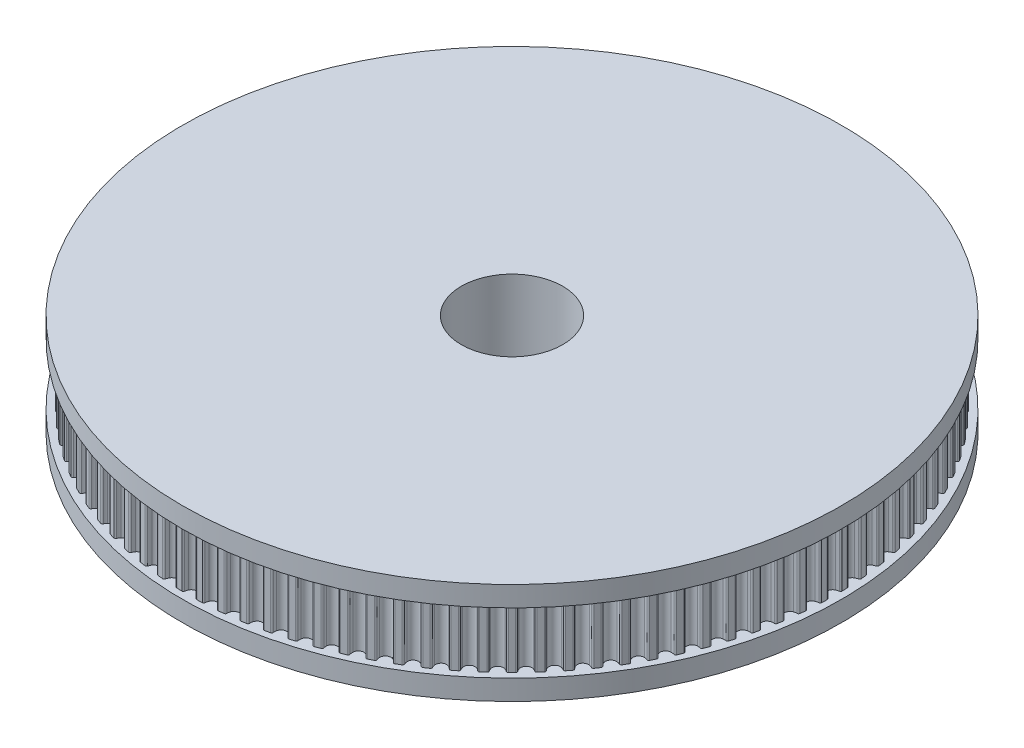
SolidWorks part; units mm, degrees
ref_plane "Front Plane" through (0, 0, 0) normal (0, 0, 1) x (1, 0, 0)
ref_plane "Top Plane" through (0, 0, 0) normal (0, 1, 0) x (1, 0, 0)
ref_plane "Right Plane" through (0, 0, 0) normal (1, 0, 0) x (0, 0, -1)
sketch "Sketch1" plane through (0, 0, 0) normal (0, 1, 0) x (1, 0, 0)
  arc A0 (-0.7485, 6.3218) -> (0.7485, 6.3218) centre (0, 0) ccw
  arc A3 (0.5071, 5.943) -> (0.5827, 6.1964) centre (-0.4049, 6.3531) ccw
  arc A4 (-0.5071, 5.943) -> (0.5071, 5.943) centre (0, 6.171) ccw
  arc A5 (-0.5827, 6.1964) -> (-0.5071, 5.943) centre (0.4049, 6.3531) ccw
  arc A6 (0.7485, 6.3218) -> (0.5827, 6.1964) centre (0.7309, 6.1729) ccw
  arc A7 (-0.7485, 6.3218) -> (-0.5827, 6.1964) centre (-0.7309, 6.1729) cw
  arc A8 (1.2417, 6.2437) -> (1.3606, 6.0732) centre (1.2124, 6.0966) cw
  arc A9 (1.3606, 6.0732) -> (1.3542, 5.8088) centre (2.3483, 5.917) ccw
  arc A10 (1.3542, 5.8088) -> (2.3187, 5.4954) centre (1.9069, 5.869) ccw
  arc A11 (2.3187, 5.4954) -> (2.469, 5.7131) centre (1.5781, 6.1673) ccw
  arc A12 (2.6654, 5.7811) -> (2.469, 5.7131) centre (2.6026, 5.6449) ccw
  arc A13 (3.1103, 5.5544) -> (3.1707, 5.3555) centre (3.0371, 5.4236) cw
  arc A14 (3.1707, 5.3555) -> (3.0829, 5.106) centre (4.0619, 4.9018) ccw
  arc A15 (3.0829, 5.106) -> (3.9034, 4.5099) centre (3.6272, 4.9924) ccw
  arc A16 (3.9034, 4.5099) -> (4.1136, 4.6705) centre (3.4067, 5.3778) ccw
  arc A17 (4.3214, 4.6745) -> (4.1136, 4.6705) centre (4.2196, 4.5644) ccw
  arc A18 (4.6745, 4.3214) -> (4.6705, 4.1136) centre (4.5644, 4.2196) cw
  arc A19 (4.6705, 4.1136) -> (4.5099, 3.9034) centre (5.3778, 3.4067) ccw
  arc A20 (4.5099, 3.9034) -> (5.106, 3.0829) centre (4.9924, 3.6272) ccw
  arc A21 (5.106, 3.0829) -> (5.3555, 3.1707) centre (4.9018, 4.0619) ccw
  arc A22 (5.5544, 3.1103) -> (5.3555, 3.1707) centre (5.4236, 3.0371) ccw
  arc A23 (5.7811, 2.6654) -> (5.7131, 2.469) centre (5.6449, 2.6026) cw
  arc A24 (5.7131, 2.469) -> (5.4954, 2.3187) centre (6.1673, 1.5781) ccw
  arc A25 (5.4954, 2.3187) -> (5.8088, 1.3542) centre (5.869, 1.9069) ccw
  arc A26 (5.8088, 1.3542) -> (6.0732, 1.3606) centre (5.917, 2.3483) ccw
  arc A27 (6.2437, 1.2417) -> (6.0732, 1.3606) centre (6.0966, 1.2124) ccw
  arc A28 (6.3218, 0.7485) -> (6.1964, 0.5827) centre (6.1729, 0.7309) cw
  arc A29 (6.1964, 0.5827) -> (5.943, 0.5071) centre (6.3531, -0.4049) ccw
  arc A30 (5.943, 0.5071) -> (5.943, -0.5071) centre (6.171, 0) ccw
  arc A31 (5.943, -0.5071) -> (6.1964, -0.5827) centre (6.3531, 0.4049) ccw
  arc A32 (6.3218, -0.7485) -> (6.1964, -0.5827) centre (6.1729, -0.7309) ccw
  arc A33 (6.2437, -1.2417) -> (6.0732, -1.3606) centre (6.0966, -1.2124) cw
  arc A34 (6.0732, -1.3606) -> (5.8088, -1.3542) centre (5.917, -2.3483) ccw
  arc A35 (5.8088, -1.3542) -> (5.4954, -2.3187) centre (5.869, -1.9069) ccw
  arc A36 (5.4954, -2.3187) -> (5.7131, -2.469) centre (6.1673, -1.5781) ccw
  arc A37 (5.7811, -2.6654) -> (5.7131, -2.469) centre (5.6449, -2.6026) ccw
  arc A38 (5.5544, -3.1103) -> (5.3555, -3.1707) centre (5.4236, -3.0371) cw
  arc A39 (5.3555, -3.1707) -> (5.106, -3.0829) centre (4.9018, -4.0619) ccw
  arc A40 (5.106, -3.0829) -> (4.5099, -3.9034) centre (4.9924, -3.6272) ccw
  arc A41 (4.5099, -3.9034) -> (4.6705, -4.1136) centre (5.3778, -3.4067) ccw
  arc A42 (4.6745, -4.3214) -> (4.6705, -4.1136) centre (4.5644, -4.2196) ccw
  arc A43 (4.3214, -4.6745) -> (4.1136, -4.6705) centre (4.2196, -4.5644) cw
  arc A44 (4.1136, -4.6705) -> (3.9034, -4.5099) centre (3.4067, -5.3778) ccw
  arc A45 (3.9034, -4.5099) -> (3.0829, -5.106) centre (3.6272, -4.9924) ccw
  arc A46 (3.0829, -5.106) -> (3.1707, -5.3555) centre (4.0619, -4.9018) ccw
  arc A47 (3.1103, -5.5544) -> (3.1707, -5.3555) centre (3.0371, -5.4236) ccw
  arc A48 (2.6654, -5.7811) -> (2.469, -5.7131) centre (2.6026, -5.6449) cw
  arc A49 (2.469, -5.7131) -> (2.3187, -5.4954) centre (1.5781, -6.1673) ccw
  arc A50 (2.3187, -5.4954) -> (1.3542, -5.8088) centre (1.9069, -5.869) ccw
  arc A51 (1.3542, -5.8088) -> (1.3606, -6.0732) centre (2.3483, -5.917) ccw
  arc A52 (1.2417, -6.2437) -> (1.3606, -6.0732) centre (1.2124, -6.0966) ccw
  arc A53 (0.7485, -6.3218) -> (0.5827, -6.1964) centre (0.7309, -6.1729) cw
  arc A54 (0.5827, -6.1964) -> (0.5071, -5.943) centre (-0.4049, -6.3531) ccw
  arc A55 (0.5071, -5.943) -> (-0.5071, -5.943) centre (0, -6.171) ccw
  arc A56 (-0.5071, -5.943) -> (-0.5827, -6.1964) centre (0.4049, -6.3531) ccw
  arc A57 (-0.7485, -6.3218) -> (-0.5827, -6.1964) centre (-0.7309, -6.1729) ccw
  arc A58 (-1.2417, -6.2437) -> (-1.3606, -6.0732) centre (-1.2124, -6.0966) cw
  arc A59 (-1.3606, -6.0732) -> (-1.3542, -5.8088) centre (-2.3483, -5.917) ccw
  arc A60 (-1.3542, -5.8088) -> (-2.3187, -5.4954) centre (-1.9069, -5.869) ccw
  arc A61 (-2.3187, -5.4954) -> (-2.469, -5.7131) centre (-1.5781, -6.1673) ccw
  arc A62 (-2.6654, -5.7811) -> (-2.469, -5.7131) centre (-2.6026, -5.6449) ccw
  arc A63 (-3.1103, -5.5544) -> (-3.1707, -5.3555) centre (-3.0371, -5.4236) cw
  arc A64 (-3.1707, -5.3555) -> (-3.0829, -5.106) centre (-4.0619, -4.9018) ccw
  arc A65 (-3.0829, -5.106) -> (-3.9034, -4.5099) centre (-3.6272, -4.9924) ccw
  arc A66 (-3.9034, -4.5099) -> (-4.1136, -4.6705) centre (-3.4067, -5.3778) ccw
  arc A67 (-4.3214, -4.6745) -> (-4.1136, -4.6705) centre (-4.2196, -4.5644) ccw
  arc A68 (-4.6745, -4.3214) -> (-4.6705, -4.1136) centre (-4.5644, -4.2196) cw
  arc A69 (-4.6705, -4.1136) -> (-4.5099, -3.9034) centre (-5.3778, -3.4067) ccw
  arc A70 (-4.5099, -3.9034) -> (-5.106, -3.0829) centre (-4.9924, -3.6272) ccw
  arc A71 (-5.106, -3.0829) -> (-5.3555, -3.1707) centre (-4.9018, -4.0619) ccw
  arc A72 (-5.5544, -3.1103) -> (-5.3555, -3.1707) centre (-5.4236, -3.0371) ccw
  arc A73 (-5.7811, -2.6654) -> (-5.7131, -2.469) centre (-5.6449, -2.6026) cw
  arc A74 (-5.7131, -2.469) -> (-5.4954, -2.3187) centre (-6.1673, -1.5781) ccw
  arc A75 (-5.4954, -2.3187) -> (-5.8088, -1.3542) centre (-5.869, -1.9069) ccw
  arc A76 (-5.8088, -1.3542) -> (-6.0732, -1.3606) centre (-5.917, -2.3483) ccw
  arc A77 (-6.2437, -1.2417) -> (-6.0732, -1.3606) centre (-6.0966, -1.2124) ccw
  arc A78 (-6.3218, -0.7485) -> (-6.1964, -0.5827) centre (-6.1729, -0.7309) cw
  arc A79 (-6.1964, -0.5827) -> (-5.943, -0.5071) centre (-6.3531, 0.4049) ccw
  arc A80 (-5.943, -0.5071) -> (-5.943, 0.5071) centre (-6.171, 0) ccw
  arc A81 (-5.943, 0.5071) -> (-6.1964, 0.5827) centre (-6.3531, -0.4049) ccw
  arc A82 (-6.3218, 0.7485) -> (-6.1964, 0.5827) centre (-6.1729, 0.7309) ccw
  arc A83 (-6.2437, 1.2417) -> (-6.0732, 1.3606) centre (-6.0966, 1.2124) cw
  arc A84 (-6.0732, 1.3606) -> (-5.8088, 1.3542) centre (-5.917, 2.3483) ccw
  arc A85 (-5.8088, 1.3542) -> (-5.4954, 2.3187) centre (-5.869, 1.9069) ccw
  arc A86 (-5.4954, 2.3187) -> (-5.7131, 2.469) centre (-6.1673, 1.5781) ccw
  arc A87 (-5.7811, 2.6654) -> (-5.7131, 2.469) centre (-5.6449, 2.6026) ccw
  arc A88 (-5.5544, 3.1103) -> (-5.3555, 3.1707) centre (-5.4236, 3.0371) cw
  arc A89 (-5.3555, 3.1707) -> (-5.106, 3.0829) centre (-4.9018, 4.0619) ccw
  arc A90 (-5.106, 3.0829) -> (-4.5099, 3.9034) centre (-4.9924, 3.6272) ccw
  arc A91 (-4.5099, 3.9034) -> (-4.6705, 4.1136) centre (-5.3778, 3.4067) ccw
  arc A92 (-4.6745, 4.3214) -> (-4.6705, 4.1136) centre (-4.5644, 4.2196) ccw
  arc A93 (-4.3214, 4.6745) -> (-4.1136, 4.6705) centre (-4.2196, 4.5644) cw
  arc A94 (-4.1136, 4.6705) -> (-3.9034, 4.5099) centre (-3.4067, 5.3778) ccw
  arc A95 (-3.9034, 4.5099) -> (-3.0829, 5.106) centre (-3.6272, 4.9924) ccw
  arc A96 (-3.0829, 5.106) -> (-3.1707, 5.3555) centre (-4.0619, 4.9018) ccw
  arc A97 (-3.1103, 5.5544) -> (-3.1707, 5.3555) centre (-3.0371, 5.4236) ccw
  arc A98 (-2.6654, 5.7811) -> (-2.469, 5.7131) centre (-2.6026, 5.6449) cw
  arc A99 (-2.469, 5.7131) -> (-2.3187, 5.4954) centre (-1.5781, 6.1673) ccw
  arc A100 (-2.3187, 5.4954) -> (-1.3542, 5.8088) centre (-1.9069, 5.869) ccw
  arc A101 (-1.3542, 5.8088) -> (-1.3606, 6.0732) centre (-2.3483, 5.917) ccw
  arc A102 (-1.2417, 6.2437) -> (-1.3606, 6.0732) centre (-1.2124, 6.0966) ccw
  circle A103 centre (0, 0) radius 5
  point P5 (0, 6.366)
  point P225 (0, 0)
  dimension "D1" = 12.732
  dimension "D2" = 0.15
  dimension "D4" = 20
  dimension "D5" = 2
  dimension "D6" = 10
  dimension "D3" = 0.195
extrude "Boss-Extrude1" add sketch "Sketch1" along normal blind 12 contours A0 A102 A101 A100 A99 A98 A97 A96 A95 A94 A93 A92 A91 A90 A89 A88 A87 A86 A85 A84 A83 A82 A81 A80 A79 A78 A77 A76 A75 A74 A73 A72 A71 A70 A69 A68 A67 A66 A65 A64 A63 A62 A61 region at (-0.7483, 0, -6.1499)
sketch "Sketch2" plane through (0, 12, 0) normal (0, 1, 0) x (1, 0, 0)
  arc A0 (-0.7427, 31.8213) -> (0.7427, 31.8213) centre (0, 0) ccw
  arc A1 (-0.501, 31.394) -> (0.501, 31.394) centre (0, 31.635) ccw
  arc A2 (0.501, 31.394) -> (0.5906, 31.6917) centre (-0.4001, 31.8275) ccw
  arc A4 (-0.5906, 31.6917) -> (-0.501, 31.394) centre (0.4001, 31.8275) ccw
  arc A5 (0.7427, 31.8213) -> (0.5906, 31.6917) centre (0.7392, 31.6714) ccw
  arc A6 (-0.7427, 31.8213) -> (-0.5906, 31.6917) centre (-0.7392, 31.6714) cw
  arc A7 (1.4005, 31.6663) -> (1.4712, 31.3635) centre (2.3978, 31.7396) ccw
  arc A8 (1.2568, 31.8052) -> (1.4005, 31.6663) centre (1.2509, 31.6553) cw
  arc A9 (1.4712, 31.3635) -> (2.4713, 31.3006) centre (1.9864, 31.5726) ccw
  arc A10 (2.4713, 31.3006) -> (2.5794, 31.5921) centre (1.5991, 31.7898) ccw
  arc A11 (2.7394, 31.7119) -> (2.5794, 31.5921) centre (2.7265, 31.5625) ccw
  arc A12 (3.386, 31.5159) -> (3.4376, 31.2092) centre (4.386, 31.5264) ccw
  arc A13 (3.2514, 31.6635) -> (3.386, 31.5159) centre (3.2361, 31.5143) cw
  arc A14 (3.4376, 31.2092) -> (4.4318, 31.0836) centre (3.9649, 31.3855) ccw
  arc A15 (4.4318, 31.0836) -> (4.558, 31.3678) centre (3.5921, 31.6267) ccw
  arc A16 (4.7252, 31.4773) -> (4.558, 31.3678) centre (4.7029, 31.329) ccw
  arc A17 (5.3583, 31.2411) -> (5.3905, 30.9318) centre (6.3569, 31.1888) ccw
  arc A18 (5.2331, 31.3969) -> (5.3583, 31.2411) centre (5.2085, 31.2489) cw
  arc A19 (5.3905, 30.9318) -> (6.3748, 30.744) centre (5.9278, 31.0747) ccw
  arc A20 (6.3748, 30.744) -> (6.5186, 31.0197) centre (5.5709, 31.3387) ccw
  arc A21 (6.6923, 31.1185) -> (6.5186, 31.0197) centre (6.6608, 30.9719) ccw
  arc A22 (7.3093, 30.843) -> (7.3221, 30.5323) centre (8.3027, 30.7281) ccw
  arc A23 (7.1942, 31.0063) -> (7.3093, 30.843) centre (7.1603, 30.8602) cw
  arc A24 (7.3221, 30.5323) -> (8.2927, 30.2831) centre (7.8673, 30.6411) ccw
  arc A25 (8.2927, 30.2831) -> (8.4535, 30.5492) centre (7.5276, 30.9271) ccw
  arc A26 (8.6331, 30.6369) -> (8.4535, 30.5492) centre (8.5924, 30.4925) ccw
  arc A27 (9.2316, 30.3231) -> (9.2248, 30.0123) centre (10.2158, 30.1461) ccw
  arc A28 (9.1269, 30.4934) -> (9.2316, 30.3231) centre (9.0839, 30.3497) cw
  arc A29 (9.2248, 30.0123) -> (10.1778, 29.7026) centre (9.7758, 30.0867) ccw
  arc A30 (10.1778, 29.7026) -> (10.355, 29.9581) centre (9.4547, 30.3934) ccw
  arc A31 (10.5397, 30.0344) -> (10.355, 29.9581) centre (10.4901, 29.8928) ccw
  arc A32 (11.1173, 29.6837) -> (11.091, 29.3738) centre (12.0885, 29.4452) ccw
  arc A33 (11.0236, 29.8602) -> (11.1173, 29.6837) centre (10.9717, 29.7194) cw
  arc A34 (11.091, 29.3738) -> (12.0227, 29.0049) centre (11.6456, 29.4135) ccw
  arc A35 (12.0227, 29.0049) -> (12.2157, 29.2488) centre (11.3445, 29.7397) ccw
  arc A36 (12.4048, 29.3133) -> (12.2157, 29.2488) centre (12.3463, 29.1752) ccw
  arc A37 (12.9593, 28.927) -> (12.9135, 28.6194) centre (13.9135, 28.628) ccw
  arc A38 (12.8768, 29.109) -> (12.9593, 28.927) centre (12.8161, 28.9719) cw
  arc A39 (12.9135, 28.6194) -> (13.8202, 28.1928) centre (13.4695, 28.6242) ccw
  arc A40 (13.8202, 28.1928) -> (14.0281, 28.4241) centre (13.1895, 28.9687) ccw
  arc A41 (14.2209, 28.4766) -> (14.0281, 28.4241) centre (14.1539, 28.3424) ccw
  arc A42 (14.75, 28.0562) -> (14.6851, 27.7521) centre (15.6836, 27.6979) ccw
  arc A43 (14.6792, 28.2431) -> (14.75, 28.0562) centre (14.61, 28.11) cw
  arc A44 (14.6851, 27.7521) -> (15.5632, 27.2694) centre (15.2403, 27.722) ccw
  arc A45 (15.5632, 27.2694) -> (15.7852, 27.4871) centre (14.9824, 28.0834) ccw
  arc A46 (15.9809, 27.5274) -> (15.7852, 27.4871) centre (15.9056, 27.3977) ccw
  arc A47 (16.4826, 27.0747) -> (16.3987, 26.7753) centre (17.3918, 26.6584) ccw
  arc A48 (16.4236, 27.2656) -> (16.4826, 27.0747) centre (16.3462, 27.1371) cw
  arc A49 (16.3987, 26.7753) -> (17.2448, 26.2383) centre (16.9509, 26.7103) ccw
  arc A50 (17.2448, 26.2383) -> (17.48, 26.4417) centre (16.7162, 27.0872) ccw
  arc A51 (17.6778, 26.4697) -> (17.48, 26.4417) centre (17.5945, 26.3449) ccw
  arc A52 (18.1501, 25.9863) -> (18.0476, 25.6927) centre (19.0314, 25.5138) ccw
  arc A53 (18.1032, 26.1806) -> (18.1501, 25.9863) centre (18.0179, 26.0572) cw
  arc A54 (18.0476, 25.6927) -> (18.8583, 25.1037) centre (18.5946, 25.5933) ccw
  arc A55 (18.8583, 25.1037) -> (19.1058, 25.292) centre (18.384, 25.9842) ccw
  arc A56 (19.305, 25.3074) -> (19.1058, 25.292) centre (19.214, 25.1882) ccw
  arc A57 (19.746, 24.7954) -> (19.6252, 24.5088) centre (20.5959, 24.2685) ccw
  arc A58 (19.7114, 24.9922) -> (19.746, 24.7954) centre (19.6185, 24.8744) cw
  arc A59 (19.6252, 24.5088) -> (20.3973, 23.8701) centre (20.1649, 24.3752) ccw
  arc A60 (20.3973, 23.8701) -> (20.6562, 24.0424) centre (19.9793, 24.7785) ccw
  arc A61 (20.856, 24.0453) -> (20.6562, 24.0424) centre (20.7577, 23.932) ccw
  arc A62 (21.2639, 23.5066) -> (21.1254, 23.2282) centre (22.0791, 22.9273) ccw
  arc A63 (21.2418, 23.7052) -> (21.2639, 23.5066) centre (21.1417, 23.5935) cw
  arc A64 (21.1254, 23.2282) -> (21.8559, 22.5422) centre (21.6556, 23.0609) ccw
  arc A65 (21.8559, 22.5422) -> (22.125, 22.698) centre (21.4957, 23.4751) ccw
  arc A66 (22.3246, 22.6883) -> (22.125, 22.698) centre (22.2194, 22.5814) ccw
  arc A67 (22.698, 22.125) -> (22.5422, 21.8559) centre (23.4751, 21.4957) ccw
  arc A68 (22.6883, 22.3246) -> (22.698, 22.125) centre (22.5814, 22.2194) cw
  arc A69 (22.5422, 21.8559) -> (23.2282, 21.1254) centre (23.0609, 21.6556) ccw
  arc A70 (23.2282, 21.1254) -> (23.5066, 21.2639) centre (22.9273, 22.0791) ccw
  arc A71 (23.7052, 21.2418) -> (23.5066, 21.2639) centre (23.5935, 21.1417) ccw
  arc A72 (24.0424, 20.6562) -> (23.8701, 20.3973) centre (24.7785, 19.9793) ccw
  arc A73 (24.0453, 20.856) -> (24.0424, 20.6562) centre (23.932, 20.7577) cw
  arc A74 (23.8701, 20.3973) -> (24.5088, 19.6252) centre (24.3752, 20.1649) ccw
  arc A75 (24.5088, 19.6252) -> (24.7954, 19.746) centre (24.2685, 20.5959) ccw
  arc A76 (24.9922, 19.7114) -> (24.7954, 19.746) centre (24.8744, 19.6185) ccw
  arc A77 (25.292, 19.1058) -> (25.1037, 18.8583) centre (25.9842, 18.384) ccw
  arc A78 (25.3074, 19.305) -> (25.292, 19.1058) centre (25.1882, 19.214) cw
  arc A79 (25.1037, 18.8583) -> (25.6927, 18.0476) centre (25.5933, 18.5946) ccw
  arc A80 (25.6927, 18.0476) -> (25.9863, 18.1501) centre (25.5138, 19.0314) ccw
  arc A81 (26.1806, 18.1032) -> (25.9863, 18.1501) centre (26.0572, 18.0179) ccw
  arc A82 (26.4417, 17.48) -> (26.2383, 17.2448) centre (27.0872, 16.7162) ccw
  arc A83 (26.4697, 17.6778) -> (26.4417, 17.48) centre (26.3449, 17.5945) cw
  arc A84 (26.2383, 17.2448) -> (26.7753, 16.3987) centre (26.7103, 16.9509) ccw
  arc A85 (26.7753, 16.3987) -> (27.0747, 16.4826) centre (26.6584, 17.3918) ccw
  arc A86 (27.2656, 16.4236) -> (27.0747, 16.4826) centre (27.1371, 16.3462) ccw
  arc A87 (27.4871, 15.7852) -> (27.2694, 15.5632) centre (28.0834, 14.9824) ccw
  arc A88 (27.5274, 15.9809) -> (27.4871, 15.7852) centre (27.3977, 15.9056) cw
  arc A89 (27.2694, 15.5632) -> (27.7521, 14.6851) centre (27.722, 15.2403) ccw
  arc A90 (27.7521, 14.6851) -> (28.0562, 14.75) centre (27.6979, 15.6836) ccw
  arc A91 (28.2431, 14.6792) -> (28.0562, 14.75) centre (28.11, 14.61) ccw
  arc A92 (28.4241, 14.0281) -> (28.1928, 13.8202) centre (28.9687, 13.1895) ccw
  arc A93 (28.4766, 14.2209) -> (28.4241, 14.0281) centre (28.3424, 14.1539) cw
  arc A94 (28.1928, 13.8202) -> (28.6194, 12.9135) centre (28.6242, 13.4695) ccw
  arc A95 (28.6194, 12.9135) -> (28.927, 12.9593) centre (28.628, 13.9135) ccw
  arc A96 (29.109, 12.8768) -> (28.927, 12.9593) centre (28.9719, 12.8161) ccw
  arc A97 (29.2488, 12.2157) -> (29.0049, 12.0227) centre (29.7397, 11.3445) ccw
  arc A98 (29.3133, 12.4048) -> (29.2488, 12.2157) centre (29.1752, 12.3463) cw
  arc A99 (29.0049, 12.0227) -> (29.3738, 11.091) centre (29.4135, 11.6456) ccw
  arc A100 (29.3738, 11.091) -> (29.6837, 11.1173) centre (29.4452, 12.0885) ccw
  arc A101 (29.8602, 11.0236) -> (29.6837, 11.1173) centre (29.7194, 10.9717) ccw
  arc A102 (29.9581, 10.355) -> (29.7026, 10.1778) centre (30.3934, 9.4547) ccw
  arc A103 (30.0344, 10.5397) -> (29.9581, 10.355) centre (29.8928, 10.4901) cw
  arc A104 (29.7026, 10.1778) -> (30.0123, 9.2248) centre (30.0867, 9.7758) ccw
  arc A105 (30.0123, 9.2248) -> (30.3231, 9.2316) centre (30.1461, 10.2158) ccw
  arc A106 (30.4934, 9.1269) -> (30.3231, 9.2316) centre (30.3497, 9.0839) ccw
  arc A107 (30.5492, 8.4535) -> (30.2831, 8.2927) centre (30.9271, 7.5276) ccw
  arc A108 (30.6369, 8.6331) -> (30.5492, 8.4535) centre (30.4925, 8.5924) cw
  arc A109 (30.2831, 8.2927) -> (30.5323, 7.3221) centre (30.6411, 7.8673) ccw
  arc A110 (30.5323, 7.3221) -> (30.843, 7.3093) centre (30.7281, 8.3027) ccw
  arc A111 (31.0063, 7.1942) -> (30.843, 7.3093) centre (30.8602, 7.1603) ccw
  arc A112 (31.0197, 6.5186) -> (30.744, 6.3748) centre (31.3387, 5.5709) ccw
  arc A113 (31.1185, 6.6923) -> (31.0197, 6.5186) centre (30.9719, 6.6608) cw
  arc A114 (30.744, 6.3748) -> (30.9318, 5.3905) centre (31.0747, 5.9278) ccw
  arc A115 (30.9318, 5.3905) -> (31.2411, 5.3583) centre (31.1888, 6.3569) ccw
  arc A116 (31.3969, 5.2331) -> (31.2411, 5.3583) centre (31.2489, 5.2085) ccw
  arc A117 (31.3678, 4.558) -> (31.0836, 4.4318) centre (31.6267, 3.5921) ccw
  arc A118 (31.4773, 4.7252) -> (31.3678, 4.558) centre (31.329, 4.7029) cw
  arc A119 (31.0836, 4.4318) -> (31.2092, 3.4376) centre (31.3855, 3.9649) ccw
  arc A120 (31.2092, 3.4376) -> (31.5159, 3.386) centre (31.5264, 4.386) ccw
  arc A121 (31.6635, 3.2514) -> (31.5159, 3.386) centre (31.5143, 3.2361) ccw
  arc A122 (31.5921, 2.5794) -> (31.3006, 2.4713) centre (31.7898, 1.5991) ccw
  arc A123 (31.7119, 2.7394) -> (31.5921, 2.5794) centre (31.5625, 2.7265) cw
  arc A124 (31.3006, 2.4713) -> (31.3635, 1.4712) centre (31.5726, 1.9864) ccw
  arc A125 (31.3635, 1.4712) -> (31.6663, 1.4005) centre (31.7396, 2.3978) ccw
  arc A126 (31.8052, 1.2568) -> (31.6663, 1.4005) centre (31.6553, 1.2509) ccw
  arc A127 (31.6917, 0.5906) -> (31.394, 0.501) centre (31.8275, -0.4001) ccw
  arc A128 (31.8213, 0.7427) -> (31.6917, 0.5906) centre (31.6714, 0.7392) cw
  arc A129 (31.394, 0.501) -> (31.394, -0.501) centre (31.635, 0) ccw
  arc A130 (31.394, -0.501) -> (31.6917, -0.5906) centre (31.8275, 0.4001) ccw
  arc A131 (31.8213, -0.7427) -> (31.6917, -0.5906) centre (31.6714, -0.7392) ccw
  arc A132 (31.6663, -1.4005) -> (31.3635, -1.4712) centre (31.7396, -2.3978) ccw
  arc A133 (31.8052, -1.2568) -> (31.6663, -1.4005) centre (31.6553, -1.2509) cw
  arc A134 (31.3635, -1.4712) -> (31.3006, -2.4713) centre (31.5726, -1.9864) ccw
  arc A135 (31.3006, -2.4713) -> (31.5921, -2.5794) centre (31.7898, -1.5991) ccw
  arc A136 (31.7119, -2.7394) -> (31.5921, -2.5794) centre (31.5625, -2.7265) ccw
  arc A137 (31.5159, -3.386) -> (31.2092, -3.4376) centre (31.5264, -4.386) ccw
  arc A138 (31.6635, -3.2514) -> (31.5159, -3.386) centre (31.5143, -3.2361) cw
  arc A139 (31.2092, -3.4376) -> (31.0836, -4.4318) centre (31.3855, -3.9649) ccw
  arc A140 (31.0836, -4.4318) -> (31.3678, -4.558) centre (31.6267, -3.5921) ccw
  arc A141 (31.4773, -4.7252) -> (31.3678, -4.558) centre (31.329, -4.7029) ccw
  arc A142 (31.2411, -5.3583) -> (30.9318, -5.3905) centre (31.1888, -6.3569) ccw
  arc A143 (31.3969, -5.2331) -> (31.2411, -5.3583) centre (31.2489, -5.2085) cw
  arc A144 (30.9318, -5.3905) -> (30.744, -6.3748) centre (31.0747, -5.9278) ccw
  arc A145 (30.744, -6.3748) -> (31.0197, -6.5186) centre (31.3387, -5.5709) ccw
  arc A146 (31.1185, -6.6923) -> (31.0197, -6.5186) centre (30.9719, -6.6608) ccw
  arc A147 (30.843, -7.3093) -> (30.5323, -7.3221) centre (30.7281, -8.3027) ccw
  arc A148 (31.0063, -7.1942) -> (30.843, -7.3093) centre (30.8602, -7.1603) cw
  arc A149 (30.5323, -7.3221) -> (30.2831, -8.2927) centre (30.6411, -7.8673) ccw
  arc A150 (30.2831, -8.2927) -> (30.5492, -8.4535) centre (30.9271, -7.5276) ccw
  arc A151 (30.6369, -8.6331) -> (30.5492, -8.4535) centre (30.4925, -8.5924) ccw
  arc A152 (30.3231, -9.2316) -> (30.0123, -9.2248) centre (30.1461, -10.2158) ccw
  arc A153 (30.4934, -9.1269) -> (30.3231, -9.2316) centre (30.3497, -9.0839) cw
  arc A154 (30.0123, -9.2248) -> (29.7026, -10.1778) centre (30.0867, -9.7758) ccw
  arc A155 (29.7026, -10.1778) -> (29.9581, -10.355) centre (30.3934, -9.4547) ccw
  arc A156 (30.0344, -10.5397) -> (29.9581, -10.355) centre (29.8928, -10.4901) ccw
  arc A157 (29.6837, -11.1173) -> (29.3738, -11.091) centre (29.4452, -12.0885) ccw
  arc A158 (29.8602, -11.0236) -> (29.6837, -11.1173) centre (29.7194, -10.9717) cw
  arc A159 (29.3738, -11.091) -> (29.0049, -12.0227) centre (29.4135, -11.6456) ccw
  arc A160 (29.0049, -12.0227) -> (29.2488, -12.2157) centre (29.7397, -11.3445) ccw
  arc A161 (29.3133, -12.4048) -> (29.2488, -12.2157) centre (29.1752, -12.3463) ccw
  arc A162 (28.927, -12.9593) -> (28.6194, -12.9135) centre (28.628, -13.9135) ccw
  arc A163 (29.109, -12.8768) -> (28.927, -12.9593) centre (28.9719, -12.8161) cw
  arc A164 (28.6194, -12.9135) -> (28.1928, -13.8202) centre (28.6242, -13.4695) ccw
  arc A165 (28.1928, -13.8202) -> (28.4241, -14.0281) centre (28.9687, -13.1895) ccw
  arc A166 (28.4766, -14.2209) -> (28.4241, -14.0281) centre (28.3424, -14.1539) ccw
  arc A167 (28.0562, -14.75) -> (27.7521, -14.6851) centre (27.6979, -15.6836) ccw
  arc A168 (28.2431, -14.6792) -> (28.0562, -14.75) centre (28.11, -14.61) cw
  arc A169 (27.7521, -14.6851) -> (27.2694, -15.5632) centre (27.722, -15.2403) ccw
  arc A170 (27.2694, -15.5632) -> (27.4871, -15.7852) centre (28.0834, -14.9824) ccw
  arc A171 (27.5274, -15.9809) -> (27.4871, -15.7852) centre (27.3977, -15.9056) ccw
  arc A172 (27.0747, -16.4826) -> (26.7753, -16.3987) centre (26.6584, -17.3918) ccw
  arc A173 (27.2656, -16.4236) -> (27.0747, -16.4826) centre (27.1371, -16.3462) cw
  arc A174 (26.7753, -16.3987) -> (26.2383, -17.2448) centre (26.7103, -16.9509) ccw
  arc A175 (26.2383, -17.2448) -> (26.4417, -17.48) centre (27.0872, -16.7162) ccw
  arc A176 (26.4697, -17.6778) -> (26.4417, -17.48) centre (26.3449, -17.5945) ccw
  arc A177 (25.9863, -18.1501) -> (25.6927, -18.0476) centre (25.5138, -19.0314) ccw
  arc A178 (26.1806, -18.1032) -> (25.9863, -18.1501) centre (26.0572, -18.0179) cw
  arc A179 (25.6927, -18.0476) -> (25.1037, -18.8583) centre (25.5933, -18.5946) ccw
  arc A180 (25.1037, -18.8583) -> (25.292, -19.1058) centre (25.9842, -18.384) ccw
  arc A181 (25.3074, -19.305) -> (25.292, -19.1058) centre (25.1882, -19.214) ccw
  arc A182 (24.7954, -19.746) -> (24.5088, -19.6252) centre (24.2685, -20.5959) ccw
  arc A183 (24.9922, -19.7114) -> (24.7954, -19.746) centre (24.8744, -19.6185) cw
  arc A184 (24.5088, -19.6252) -> (23.8701, -20.3973) centre (24.3752, -20.1649) ccw
  arc A185 (23.8701, -20.3973) -> (24.0424, -20.6562) centre (24.7785, -19.9793) ccw
  arc A186 (24.0453, -20.856) -> (24.0424, -20.6562) centre (23.932, -20.7577) ccw
  arc A187 (23.5066, -21.2639) -> (23.2282, -21.1254) centre (22.9273, -22.0791) ccw
  arc A188 (23.7052, -21.2418) -> (23.5066, -21.2639) centre (23.5935, -21.1417) cw
  arc A189 (23.2282, -21.1254) -> (22.5422, -21.8559) centre (23.0609, -21.6556) ccw
  arc A190 (22.5422, -21.8559) -> (22.698, -22.125) centre (23.4751, -21.4957) ccw
  arc A191 (22.6883, -22.3246) -> (22.698, -22.125) centre (22.5814, -22.2194) ccw
  arc A192 (22.125, -22.698) -> (21.8559, -22.5422) centre (21.4957, -23.4751) ccw
  arc A193 (22.3246, -22.6883) -> (22.125, -22.698) centre (22.2194, -22.5814) cw
  arc A194 (21.8559, -22.5422) -> (21.1254, -23.2282) centre (21.6556, -23.0609) ccw
  arc A195 (21.1254, -23.2282) -> (21.2639, -23.5066) centre (22.0791, -22.9273) ccw
  arc A196 (21.2418, -23.7052) -> (21.2639, -23.5066) centre (21.1417, -23.5935) ccw
  arc A197 (20.6562, -24.0424) -> (20.3973, -23.8701) centre (19.9793, -24.7785) ccw
  arc A198 (20.856, -24.0453) -> (20.6562, -24.0424) centre (20.7577, -23.932) cw
  arc A199 (20.3973, -23.8701) -> (19.6252, -24.5088) centre (20.1649, -24.3752) ccw
  arc A200 (19.6252, -24.5088) -> (19.746, -24.7954) centre (20.5959, -24.2685) ccw
  arc A201 (19.7114, -24.9922) -> (19.746, -24.7954) centre (19.6185, -24.8744) ccw
  arc A202 (19.1058, -25.292) -> (18.8583, -25.1037) centre (18.384, -25.9842) ccw
  arc A203 (19.305, -25.3074) -> (19.1058, -25.292) centre (19.214, -25.1882) cw
  arc A204 (18.8583, -25.1037) -> (18.0476, -25.6927) centre (18.5946, -25.5933) ccw
  arc A205 (18.0476, -25.6927) -> (18.1501, -25.9863) centre (19.0314, -25.5138) ccw
  arc A206 (18.1032, -26.1806) -> (18.1501, -25.9863) centre (18.0179, -26.0572) ccw
  arc A207 (17.48, -26.4417) -> (17.2448, -26.2383) centre (16.7162, -27.0872) ccw
  arc A208 (17.6778, -26.4697) -> (17.48, -26.4417) centre (17.5945, -26.3449) cw
  arc A209 (17.2448, -26.2383) -> (16.3987, -26.7753) centre (16.9509, -26.7103) ccw
  arc A210 (16.3987, -26.7753) -> (16.4826, -27.0747) centre (17.3918, -26.6584) ccw
  arc A211 (16.4236, -27.2656) -> (16.4826, -27.0747) centre (16.3462, -27.1371) ccw
  arc A212 (15.7852, -27.4871) -> (15.5632, -27.2694) centre (14.9824, -28.0834) ccw
  arc A213 (15.9809, -27.5274) -> (15.7852, -27.4871) centre (15.9056, -27.3977) cw
  arc A214 (15.5632, -27.2694) -> (14.6851, -27.7521) centre (15.2403, -27.722) ccw
  arc A215 (14.6851, -27.7521) -> (14.75, -28.0562) centre (15.6836, -27.6979) ccw
  arc A216 (14.6792, -28.2431) -> (14.75, -28.0562) centre (14.61, -28.11) ccw
  arc A217 (14.0281, -28.4241) -> (13.8202, -28.1928) centre (13.1895, -28.9687) ccw
  arc A218 (14.2209, -28.4766) -> (14.0281, -28.4241) centre (14.1539, -28.3424) cw
  arc A219 (13.8202, -28.1928) -> (12.9135, -28.6194) centre (13.4695, -28.6242) ccw
  arc A220 (12.9135, -28.6194) -> (12.9593, -28.927) centre (13.9135, -28.628) ccw
  arc A221 (12.8768, -29.109) -> (12.9593, -28.927) centre (12.8161, -28.9719) ccw
  arc A222 (12.2157, -29.2488) -> (12.0227, -29.0049) centre (11.3445, -29.7397) ccw
  arc A223 (12.4048, -29.3133) -> (12.2157, -29.2488) centre (12.3463, -29.1752) cw
  arc A224 (12.0227, -29.0049) -> (11.091, -29.3738) centre (11.6456, -29.4135) ccw
  arc A225 (11.091, -29.3738) -> (11.1173, -29.6837) centre (12.0885, -29.4452) ccw
  arc A226 (11.0236, -29.8602) -> (11.1173, -29.6837) centre (10.9717, -29.7194) ccw
  arc A227 (10.355, -29.9581) -> (10.1778, -29.7026) centre (9.4547, -30.3934) ccw
  arc A228 (10.5397, -30.0344) -> (10.355, -29.9581) centre (10.4901, -29.8928) cw
  arc A229 (10.1778, -29.7026) -> (9.2248, -30.0123) centre (9.7758, -30.0867) ccw
  arc A230 (9.2248, -30.0123) -> (9.2316, -30.3231) centre (10.2158, -30.1461) ccw
  arc A231 (9.1269, -30.4934) -> (9.2316, -30.3231) centre (9.0839, -30.3497) ccw
  arc A232 (8.4535, -30.5492) -> (8.2927, -30.2831) centre (7.5276, -30.9271) ccw
  arc A233 (8.6331, -30.6369) -> (8.4535, -30.5492) centre (8.5924, -30.4925) cw
  arc A234 (8.2927, -30.2831) -> (7.3221, -30.5323) centre (7.8673, -30.6411) ccw
  arc A235 (7.3221, -30.5323) -> (7.3093, -30.843) centre (8.3027, -30.7281) ccw
  arc A236 (7.1942, -31.0063) -> (7.3093, -30.843) centre (7.1603, -30.8602) ccw
  arc A237 (6.5186, -31.0197) -> (6.3748, -30.744) centre (5.5709, -31.3387) ccw
  arc A238 (6.6923, -31.1185) -> (6.5186, -31.0197) centre (6.6608, -30.9719) cw
  arc A239 (6.3748, -30.744) -> (5.3905, -30.9318) centre (5.9278, -31.0747) ccw
  arc A240 (5.3905, -30.9318) -> (5.3583, -31.2411) centre (6.3569, -31.1888) ccw
  arc A241 (5.2331, -31.3969) -> (5.3583, -31.2411) centre (5.2085, -31.2489) ccw
  arc A242 (4.558, -31.3678) -> (4.4318, -31.0836) centre (3.5921, -31.6267) ccw
  arc A243 (4.7252, -31.4773) -> (4.558, -31.3678) centre (4.7029, -31.329) cw
  arc A244 (4.4318, -31.0836) -> (3.4376, -31.2092) centre (3.9649, -31.3855) ccw
  arc A245 (3.4376, -31.2092) -> (3.386, -31.5159) centre (4.386, -31.5264) ccw
  arc A246 (3.2514, -31.6635) -> (3.386, -31.5159) centre (3.2361, -31.5143) ccw
  arc A247 (2.5794, -31.5921) -> (2.4713, -31.3006) centre (1.5991, -31.7898) ccw
  arc A248 (2.7394, -31.7119) -> (2.5794, -31.5921) centre (2.7265, -31.5625) cw
  arc A249 (2.4713, -31.3006) -> (1.4712, -31.3635) centre (1.9864, -31.5726) ccw
  arc A250 (1.4712, -31.3635) -> (1.4005, -31.6663) centre (2.3978, -31.7396) ccw
  arc A251 (1.2568, -31.8052) -> (1.4005, -31.6663) centre (1.2509, -31.6553) ccw
  arc A252 (0.5906, -31.6917) -> (0.501, -31.394) centre (-0.4001, -31.8275) ccw
  arc A253 (0.7427, -31.8213) -> (0.5906, -31.6917) centre (0.7392, -31.6714) cw
  arc A254 (0.501, -31.394) -> (-0.501, -31.394) centre (0, -31.635) ccw
  arc A255 (-0.501, -31.394) -> (-0.5906, -31.6917) centre (0.4001, -31.8275) ccw
  arc A256 (-0.7427, -31.8213) -> (-0.5906, -31.6917) centre (-0.7392, -31.6714) ccw
  arc A257 (-1.4005, -31.6663) -> (-1.4712, -31.3635) centre (-2.3978, -31.7396) ccw
  arc A258 (-1.2568, -31.8052) -> (-1.4005, -31.6663) centre (-1.2509, -31.6553) cw
  arc A259 (-1.4712, -31.3635) -> (-2.4713, -31.3006) centre (-1.9864, -31.5726) ccw
  arc A260 (-2.4713, -31.3006) -> (-2.5794, -31.5921) centre (-1.5991, -31.7898) ccw
  arc A261 (-2.7394, -31.7119) -> (-2.5794, -31.5921) centre (-2.7265, -31.5625) ccw
  arc A262 (-3.386, -31.5159) -> (-3.4376, -31.2092) centre (-4.386, -31.5264) ccw
  arc A263 (-3.2514, -31.6635) -> (-3.386, -31.5159) centre (-3.2361, -31.5143) cw
  arc A264 (-3.4376, -31.2092) -> (-4.4318, -31.0836) centre (-3.9649, -31.3855) ccw
  arc A265 (-4.4318, -31.0836) -> (-4.558, -31.3678) centre (-3.5921, -31.6267) ccw
  arc A266 (-4.7252, -31.4773) -> (-4.558, -31.3678) centre (-4.7029, -31.329) ccw
  arc A267 (-5.3583, -31.2411) -> (-5.3905, -30.9318) centre (-6.3569, -31.1888) ccw
  arc A268 (-5.2331, -31.3969) -> (-5.3583, -31.2411) centre (-5.2085, -31.2489) cw
  arc A269 (-5.3905, -30.9318) -> (-6.3748, -30.744) centre (-5.9278, -31.0747) ccw
  arc A270 (-6.3748, -30.744) -> (-6.5186, -31.0197) centre (-5.5709, -31.3387) ccw
  arc A271 (-6.6923, -31.1185) -> (-6.5186, -31.0197) centre (-6.6608, -30.9719) ccw
  arc A272 (-7.3093, -30.843) -> (-7.3221, -30.5323) centre (-8.3027, -30.7281) ccw
  arc A273 (-7.1942, -31.0063) -> (-7.3093, -30.843) centre (-7.1603, -30.8602) cw
  arc A274 (-7.3221, -30.5323) -> (-8.2927, -30.2831) centre (-7.8673, -30.6411) ccw
  arc A275 (-8.2927, -30.2831) -> (-8.4535, -30.5492) centre (-7.5276, -30.9271) ccw
  arc A276 (-8.6331, -30.6369) -> (-8.4535, -30.5492) centre (-8.5924, -30.4925) ccw
  arc A277 (-9.2316, -30.3231) -> (-9.2248, -30.0123) centre (-10.2158, -30.1461) ccw
  arc A278 (-9.1269, -30.4934) -> (-9.2316, -30.3231) centre (-9.0839, -30.3497) cw
  arc A279 (-9.2248, -30.0123) -> (-10.1778, -29.7026) centre (-9.7758, -30.0867) ccw
  arc A280 (-10.1778, -29.7026) -> (-10.355, -29.9581) centre (-9.4547, -30.3934) ccw
  arc A281 (-10.5397, -30.0344) -> (-10.355, -29.9581) centre (-10.4901, -29.8928) ccw
  arc A282 (-11.1173, -29.6837) -> (-11.091, -29.3738) centre (-12.0885, -29.4452) ccw
  arc A283 (-11.0236, -29.8602) -> (-11.1173, -29.6837) centre (-10.9717, -29.7194) cw
  arc A284 (-11.091, -29.3738) -> (-12.0227, -29.0049) centre (-11.6456, -29.4135) ccw
  arc A285 (-12.0227, -29.0049) -> (-12.2157, -29.2488) centre (-11.3445, -29.7397) ccw
  arc A286 (-12.4048, -29.3133) -> (-12.2157, -29.2488) centre (-12.3463, -29.1752) ccw
  arc A287 (-12.9593, -28.927) -> (-12.9135, -28.6194) centre (-13.9135, -28.628) ccw
  arc A288 (-12.8768, -29.109) -> (-12.9593, -28.927) centre (-12.8161, -28.9719) cw
  arc A289 (-12.9135, -28.6194) -> (-13.8202, -28.1928) centre (-13.4695, -28.6242) ccw
  arc A290 (-13.8202, -28.1928) -> (-14.0281, -28.4241) centre (-13.1895, -28.9687) ccw
  arc A291 (-14.2209, -28.4766) -> (-14.0281, -28.4241) centre (-14.1539, -28.3424) ccw
  arc A292 (-14.75, -28.0562) -> (-14.6851, -27.7521) centre (-15.6836, -27.6979) ccw
  arc A293 (-14.6792, -28.2431) -> (-14.75, -28.0562) centre (-14.61, -28.11) cw
  arc A294 (-14.6851, -27.7521) -> (-15.5632, -27.2694) centre (-15.2403, -27.722) ccw
  arc A295 (-15.5632, -27.2694) -> (-15.7852, -27.4871) centre (-14.9824, -28.0834) ccw
  arc A296 (-15.9809, -27.5274) -> (-15.7852, -27.4871) centre (-15.9056, -27.3977) ccw
  arc A297 (-16.4826, -27.0747) -> (-16.3987, -26.7753) centre (-17.3918, -26.6584) ccw
  arc A298 (-16.4236, -27.2656) -> (-16.4826, -27.0747) centre (-16.3462, -27.1371) cw
  arc A299 (-16.3987, -26.7753) -> (-17.2448, -26.2383) centre (-16.9509, -26.7103) ccw
  arc A300 (-17.2448, -26.2383) -> (-17.48, -26.4417) centre (-16.7162, -27.0872) ccw
  arc A301 (-17.6778, -26.4697) -> (-17.48, -26.4417) centre (-17.5945, -26.3449) ccw
  arc A302 (-18.1501, -25.9863) -> (-18.0476, -25.6927) centre (-19.0314, -25.5138) ccw
  arc A303 (-18.1032, -26.1806) -> (-18.1501, -25.9863) centre (-18.0179, -26.0572) cw
  arc A304 (-18.0476, -25.6927) -> (-18.8583, -25.1037) centre (-18.5946, -25.5933) ccw
  arc A305 (-18.8583, -25.1037) -> (-19.1058, -25.292) centre (-18.384, -25.9842) ccw
  arc A306 (-19.305, -25.3074) -> (-19.1058, -25.292) centre (-19.214, -25.1882) ccw
  arc A307 (-19.746, -24.7954) -> (-19.6252, -24.5088) centre (-20.5959, -24.2685) ccw
  arc A308 (-19.7114, -24.9922) -> (-19.746, -24.7954) centre (-19.6185, -24.8744) cw
  arc A309 (-19.6252, -24.5088) -> (-20.3973, -23.8701) centre (-20.1649, -24.3752) ccw
  arc A310 (-20.3973, -23.8701) -> (-20.6562, -24.0424) centre (-19.9793, -24.7785) ccw
  arc A311 (-20.856, -24.0453) -> (-20.6562, -24.0424) centre (-20.7577, -23.932) ccw
  arc A312 (-21.2639, -23.5066) -> (-21.1254, -23.2282) centre (-22.0791, -22.9273) ccw
  arc A313 (-21.2418, -23.7052) -> (-21.2639, -23.5066) centre (-21.1417, -23.5935) cw
  arc A314 (-21.1254, -23.2282) -> (-21.8559, -22.5422) centre (-21.6556, -23.0609) ccw
  arc A315 (-21.8559, -22.5422) -> (-22.125, -22.698) centre (-21.4957, -23.4751) ccw
  arc A316 (-22.3246, -22.6883) -> (-22.125, -22.698) centre (-22.2194, -22.5814) ccw
  arc A317 (-22.698, -22.125) -> (-22.5422, -21.8559) centre (-23.4751, -21.4957) ccw
  arc A318 (-22.6883, -22.3246) -> (-22.698, -22.125) centre (-22.5814, -22.2194) cw
  arc A319 (-22.5422, -21.8559) -> (-23.2282, -21.1254) centre (-23.0609, -21.6556) ccw
  arc A320 (-23.2282, -21.1254) -> (-23.5066, -21.2639) centre (-22.9273, -22.0791) ccw
  arc A321 (-23.7052, -21.2418) -> (-23.5066, -21.2639) centre (-23.5935, -21.1417) ccw
  arc A322 (-24.0424, -20.6562) -> (-23.8701, -20.3973) centre (-24.7785, -19.9793) ccw
  arc A323 (-24.0453, -20.856) -> (-24.0424, -20.6562) centre (-23.932, -20.7577) cw
  arc A324 (-23.8701, -20.3973) -> (-24.5088, -19.6252) centre (-24.3752, -20.1649) ccw
  arc A325 (-24.5088, -19.6252) -> (-24.7954, -19.746) centre (-24.2685, -20.5959) ccw
  arc A326 (-24.9922, -19.7114) -> (-24.7954, -19.746) centre (-24.8744, -19.6185) ccw
  arc A327 (-25.292, -19.1058) -> (-25.1037, -18.8583) centre (-25.9842, -18.384) ccw
  arc A328 (-25.3074, -19.305) -> (-25.292, -19.1058) centre (-25.1882, -19.214) cw
  arc A329 (-25.1037, -18.8583) -> (-25.6927, -18.0476) centre (-25.5933, -18.5946) ccw
  arc A330 (-25.6927, -18.0476) -> (-25.9863, -18.1501) centre (-25.5138, -19.0314) ccw
  arc A331 (-26.1806, -18.1032) -> (-25.9863, -18.1501) centre (-26.0572, -18.0179) ccw
  arc A332 (-26.4417, -17.48) -> (-26.2383, -17.2448) centre (-27.0872, -16.7162) ccw
  arc A333 (-26.4697, -17.6778) -> (-26.4417, -17.48) centre (-26.3449, -17.5945) cw
  arc A334 (-26.2383, -17.2448) -> (-26.7753, -16.3987) centre (-26.7103, -16.9509) ccw
  arc A335 (-26.7753, -16.3987) -> (-27.0747, -16.4826) centre (-26.6584, -17.3918) ccw
  arc A336 (-27.2656, -16.4236) -> (-27.0747, -16.4826) centre (-27.1371, -16.3462) ccw
  arc A337 (-27.4871, -15.7852) -> (-27.2694, -15.5632) centre (-28.0834, -14.9824) ccw
  arc A338 (-27.5274, -15.9809) -> (-27.4871, -15.7852) centre (-27.3977, -15.9056) cw
  arc A339 (-27.2694, -15.5632) -> (-27.7521, -14.6851) centre (-27.722, -15.2403) ccw
  arc A340 (-27.7521, -14.6851) -> (-28.0562, -14.75) centre (-27.6979, -15.6836) ccw
  arc A341 (-28.2431, -14.6792) -> (-28.0562, -14.75) centre (-28.11, -14.61) ccw
  arc A342 (-28.4241, -14.0281) -> (-28.1928, -13.8202) centre (-28.9687, -13.1895) ccw
  arc A343 (-28.4766, -14.2209) -> (-28.4241, -14.0281) centre (-28.3424, -14.1539) cw
  arc A344 (-28.1928, -13.8202) -> (-28.6194, -12.9135) centre (-28.6242, -13.4695) ccw
  arc A345 (-28.6194, -12.9135) -> (-28.927, -12.9593) centre (-28.628, -13.9135) ccw
  arc A346 (-29.109, -12.8768) -> (-28.927, -12.9593) centre (-28.9719, -12.8161) ccw
  arc A347 (-29.2488, -12.2157) -> (-29.0049, -12.0227) centre (-29.7397, -11.3445) ccw
  arc A348 (-29.3133, -12.4048) -> (-29.2488, -12.2157) centre (-29.1752, -12.3463) cw
  arc A349 (-29.0049, -12.0227) -> (-29.3738, -11.091) centre (-29.4135, -11.6456) ccw
  arc A350 (-29.3738, -11.091) -> (-29.6837, -11.1173) centre (-29.4452, -12.0885) ccw
  arc A351 (-29.8602, -11.0236) -> (-29.6837, -11.1173) centre (-29.7194, -10.9717) ccw
  arc A352 (-29.9581, -10.355) -> (-29.7026, -10.1778) centre (-30.3934, -9.4547) ccw
  arc A353 (-30.0344, -10.5397) -> (-29.9581, -10.355) centre (-29.8928, -10.4901) cw
  arc A354 (-29.7026, -10.1778) -> (-30.0123, -9.2248) centre (-30.0867, -9.7758) ccw
  arc A355 (-30.0123, -9.2248) -> (-30.3231, -9.2316) centre (-30.1461, -10.2158) ccw
  arc A356 (-30.4934, -9.1269) -> (-30.3231, -9.2316) centre (-30.3497, -9.0839) ccw
  arc A357 (-30.5492, -8.4535) -> (-30.2831, -8.2927) centre (-30.9271, -7.5276) ccw
  arc A358 (-30.6369, -8.6331) -> (-30.5492, -8.4535) centre (-30.4925, -8.5924) cw
  arc A359 (-30.2831, -8.2927) -> (-30.5323, -7.3221) centre (-30.6411, -7.8673) ccw
  arc A360 (-30.5323, -7.3221) -> (-30.843, -7.3093) centre (-30.7281, -8.3027) ccw
  arc A361 (-31.0063, -7.1942) -> (-30.843, -7.3093) centre (-30.8602, -7.1603) ccw
  arc A362 (-31.0197, -6.5186) -> (-30.744, -6.3748) centre (-31.3387, -5.5709) ccw
  arc A363 (-31.1185, -6.6923) -> (-31.0197, -6.5186) centre (-30.9719, -6.6608) cw
  arc A364 (-30.744, -6.3748) -> (-30.9318, -5.3905) centre (-31.0747, -5.9278) ccw
  arc A365 (-30.9318, -5.3905) -> (-31.2411, -5.3583) centre (-31.1888, -6.3569) ccw
  arc A366 (-31.3969, -5.2331) -> (-31.2411, -5.3583) centre (-31.2489, -5.2085) ccw
  arc A367 (-31.3678, -4.558) -> (-31.0836, -4.4318) centre (-31.6267, -3.5921) ccw
  arc A368 (-31.4773, -4.7252) -> (-31.3678, -4.558) centre (-31.329, -4.7029) cw
  arc A369 (-31.0836, -4.4318) -> (-31.2092, -3.4376) centre (-31.3855, -3.9649) ccw
  arc A370 (-31.2092, -3.4376) -> (-31.5159, -3.386) centre (-31.5264, -4.386) ccw
  arc A371 (-31.6635, -3.2514) -> (-31.5159, -3.386) centre (-31.5143, -3.2361) ccw
  arc A372 (-31.5921, -2.5794) -> (-31.3006, -2.4713) centre (-31.7898, -1.5991) ccw
  arc A373 (-31.7119, -2.7394) -> (-31.5921, -2.5794) centre (-31.5625, -2.7265) cw
  arc A374 (-31.3006, -2.4713) -> (-31.3635, -1.4712) centre (-31.5726, -1.9864) ccw
  arc A375 (-31.3635, -1.4712) -> (-31.6663, -1.4005) centre (-31.7396, -2.3978) ccw
  arc A376 (-31.8052, -1.2568) -> (-31.6663, -1.4005) centre (-31.6553, -1.2509) ccw
  arc A377 (-31.6917, -0.5906) -> (-31.394, -0.501) centre (-31.8275, 0.4001) ccw
  arc A378 (-31.8213, -0.7427) -> (-31.6917, -0.5906) centre (-31.6714, -0.7392) cw
  arc A379 (-31.394, -0.501) -> (-31.394, 0.501) centre (-31.635, 0) ccw
  arc A380 (-31.394, 0.501) -> (-31.6917, 0.5906) centre (-31.8275, -0.4001) ccw
  arc A381 (-31.8213, 0.7427) -> (-31.6917, 0.5906) centre (-31.6714, 0.7392) ccw
  arc A382 (-31.6663, 1.4005) -> (-31.3635, 1.4712) centre (-31.7396, 2.3978) ccw
  arc A383 (-31.8052, 1.2568) -> (-31.6663, 1.4005) centre (-31.6553, 1.2509) cw
  arc A384 (-31.3635, 1.4712) -> (-31.3006, 2.4713) centre (-31.5726, 1.9864) ccw
  arc A385 (-31.3006, 2.4713) -> (-31.5921, 2.5794) centre (-31.7898, 1.5991) ccw
  arc A386 (-31.7119, 2.7394) -> (-31.5921, 2.5794) centre (-31.5625, 2.7265) ccw
  arc A387 (-31.5159, 3.386) -> (-31.2092, 3.4376) centre (-31.5264, 4.386) ccw
  arc A388 (-31.6635, 3.2514) -> (-31.5159, 3.386) centre (-31.5143, 3.2361) cw
  arc A389 (-31.2092, 3.4376) -> (-31.0836, 4.4318) centre (-31.3855, 3.9649) ccw
  arc A390 (-31.0836, 4.4318) -> (-31.3678, 4.558) centre (-31.6267, 3.5921) ccw
  arc A391 (-31.4773, 4.7252) -> (-31.3678, 4.558) centre (-31.329, 4.7029) ccw
  arc A392 (-31.2411, 5.3583) -> (-30.9318, 5.3905) centre (-31.1888, 6.3569) ccw
  arc A393 (-31.3969, 5.2331) -> (-31.2411, 5.3583) centre (-31.2489, 5.2085) cw
  arc A394 (-30.9318, 5.3905) -> (-30.744, 6.3748) centre (-31.0747, 5.9278) ccw
  arc A395 (-30.744, 6.3748) -> (-31.0197, 6.5186) centre (-31.3387, 5.5709) ccw
  arc A396 (-31.1185, 6.6923) -> (-31.0197, 6.5186) centre (-30.9719, 6.6608) ccw
  arc A397 (-30.843, 7.3093) -> (-30.5323, 7.3221) centre (-30.7281, 8.3027) ccw
  arc A398 (-31.0063, 7.1942) -> (-30.843, 7.3093) centre (-30.8602, 7.1603) cw
  arc A399 (-30.5323, 7.3221) -> (-30.2831, 8.2927) centre (-30.6411, 7.8673) ccw
  arc A400 (-30.2831, 8.2927) -> (-30.5492, 8.4535) centre (-30.9271, 7.5276) ccw
  arc A401 (-30.6369, 8.6331) -> (-30.5492, 8.4535) centre (-30.4925, 8.5924) ccw
  arc A402 (-30.3231, 9.2316) -> (-30.0123, 9.2248) centre (-30.1461, 10.2158) ccw
  arc A403 (-30.4934, 9.1269) -> (-30.3231, 9.2316) centre (-30.3497, 9.0839) cw
  arc A404 (-30.0123, 9.2248) -> (-29.7026, 10.1778) centre (-30.0867, 9.7758) ccw
  arc A405 (-29.7026, 10.1778) -> (-29.9581, 10.355) centre (-30.3934, 9.4547) ccw
  arc A406 (-30.0344, 10.5397) -> (-29.9581, 10.355) centre (-29.8928, 10.4901) ccw
  arc A407 (-29.6837, 11.1173) -> (-29.3738, 11.091) centre (-29.4452, 12.0885) ccw
  arc A408 (-29.8602, 11.0236) -> (-29.6837, 11.1173) centre (-29.7194, 10.9717) cw
  arc A409 (-29.3738, 11.091) -> (-29.0049, 12.0227) centre (-29.4135, 11.6456) ccw
  arc A410 (-29.0049, 12.0227) -> (-29.2488, 12.2157) centre (-29.7397, 11.3445) ccw
  arc A411 (-29.3133, 12.4048) -> (-29.2488, 12.2157) centre (-29.1752, 12.3463) ccw
  arc A412 (-28.927, 12.9593) -> (-28.6194, 12.9135) centre (-28.628, 13.9135) ccw
  arc A413 (-29.109, 12.8768) -> (-28.927, 12.9593) centre (-28.9719, 12.8161) cw
  arc A414 (-28.6194, 12.9135) -> (-28.1928, 13.8202) centre (-28.6242, 13.4695) ccw
  arc A415 (-28.1928, 13.8202) -> (-28.4241, 14.0281) centre (-28.9687, 13.1895) ccw
  arc A416 (-28.4766, 14.2209) -> (-28.4241, 14.0281) centre (-28.3424, 14.1539) ccw
  arc A417 (-28.0562, 14.75) -> (-27.7521, 14.6851) centre (-27.6979, 15.6836) ccw
  arc A418 (-28.2431, 14.6792) -> (-28.0562, 14.75) centre (-28.11, 14.61) cw
  arc A419 (-27.7521, 14.6851) -> (-27.2694, 15.5632) centre (-27.722, 15.2403) ccw
  arc A420 (-27.2694, 15.5632) -> (-27.4871, 15.7852) centre (-28.0834, 14.9824) ccw
  arc A421 (-27.5274, 15.9809) -> (-27.4871, 15.7852) centre (-27.3977, 15.9056) ccw
  arc A422 (-27.0747, 16.4826) -> (-26.7753, 16.3987) centre (-26.6584, 17.3918) ccw
  arc A423 (-27.2656, 16.4236) -> (-27.0747, 16.4826) centre (-27.1371, 16.3462) cw
  arc A424 (-26.7753, 16.3987) -> (-26.2383, 17.2448) centre (-26.7103, 16.9509) ccw
  arc A425 (-26.2383, 17.2448) -> (-26.4417, 17.48) centre (-27.0872, 16.7162) ccw
  arc A426 (-26.4697, 17.6778) -> (-26.4417, 17.48) centre (-26.3449, 17.5945) ccw
  arc A427 (-25.9863, 18.1501) -> (-25.6927, 18.0476) centre (-25.5138, 19.0314) ccw
  arc A428 (-26.1806, 18.1032) -> (-25.9863, 18.1501) centre (-26.0572, 18.0179) cw
  arc A429 (-25.6927, 18.0476) -> (-25.1037, 18.8583) centre (-25.5933, 18.5946) ccw
  arc A430 (-25.1037, 18.8583) -> (-25.292, 19.1058) centre (-25.9842, 18.384) ccw
  arc A431 (-25.3074, 19.305) -> (-25.292, 19.1058) centre (-25.1882, 19.214) ccw
  arc A432 (-24.7954, 19.746) -> (-24.5088, 19.6252) centre (-24.2685, 20.5959) ccw
  arc A433 (-24.9922, 19.7114) -> (-24.7954, 19.746) centre (-24.8744, 19.6185) cw
  arc A434 (-24.5088, 19.6252) -> (-23.8701, 20.3973) centre (-24.3752, 20.1649) ccw
  arc A435 (-23.8701, 20.3973) -> (-24.0424, 20.6562) centre (-24.7785, 19.9793) ccw
  arc A436 (-24.0453, 20.856) -> (-24.0424, 20.6562) centre (-23.932, 20.7577) ccw
  arc A437 (-23.5066, 21.2639) -> (-23.2282, 21.1254) centre (-22.9273, 22.0791) ccw
  arc A438 (-23.7052, 21.2418) -> (-23.5066, 21.2639) centre (-23.5935, 21.1417) cw
  arc A439 (-23.2282, 21.1254) -> (-22.5422, 21.8559) centre (-23.0609, 21.6556) ccw
  arc A440 (-22.5422, 21.8559) -> (-22.698, 22.125) centre (-23.4751, 21.4957) ccw
  arc A441 (-22.6883, 22.3246) -> (-22.698, 22.125) centre (-22.5814, 22.2194) ccw
  arc A442 (-22.125, 22.698) -> (-21.8559, 22.5422) centre (-21.4957, 23.4751) ccw
  arc A443 (-22.3246, 22.6883) -> (-22.125, 22.698) centre (-22.2194, 22.5814) cw
  arc A444 (-21.8559, 22.5422) -> (-21.1254, 23.2282) centre (-21.6556, 23.0609) ccw
  arc A445 (-21.1254, 23.2282) -> (-21.2639, 23.5066) centre (-22.0791, 22.9273) ccw
  arc A446 (-21.2418, 23.7052) -> (-21.2639, 23.5066) centre (-21.1417, 23.5935) ccw
  arc A447 (-20.6562, 24.0424) -> (-20.3973, 23.8701) centre (-19.9793, 24.7785) ccw
  arc A448 (-20.856, 24.0453) -> (-20.6562, 24.0424) centre (-20.7577, 23.932) cw
  arc A449 (-20.3973, 23.8701) -> (-19.6252, 24.5088) centre (-20.1649, 24.3752) ccw
  arc A450 (-19.6252, 24.5088) -> (-19.746, 24.7954) centre (-20.5959, 24.2685) ccw
  arc A451 (-19.7114, 24.9922) -> (-19.746, 24.7954) centre (-19.6185, 24.8744) ccw
  arc A452 (-19.1058, 25.292) -> (-18.8583, 25.1037) centre (-18.384, 25.9842) ccw
  arc A453 (-19.305, 25.3074) -> (-19.1058, 25.292) centre (-19.214, 25.1882) cw
  arc A454 (-18.8583, 25.1037) -> (-18.0476, 25.6927) centre (-18.5946, 25.5933) ccw
  arc A455 (-18.0476, 25.6927) -> (-18.1501, 25.9863) centre (-19.0314, 25.5138) ccw
  arc A456 (-18.1032, 26.1806) -> (-18.1501, 25.9863) centre (-18.0179, 26.0572) ccw
  arc A457 (-17.48, 26.4417) -> (-17.2448, 26.2383) centre (-16.7162, 27.0872) ccw
  arc A458 (-17.6778, 26.4697) -> (-17.48, 26.4417) centre (-17.5945, 26.3449) cw
  arc A459 (-17.2448, 26.2383) -> (-16.3987, 26.7753) centre (-16.9509, 26.7103) ccw
  arc A460 (-16.3987, 26.7753) -> (-16.4826, 27.0747) centre (-17.3918, 26.6584) ccw
  arc A461 (-16.4236, 27.2656) -> (-16.4826, 27.0747) centre (-16.3462, 27.1371) ccw
  arc A462 (-15.7852, 27.4871) -> (-15.5632, 27.2694) centre (-14.9824, 28.0834) ccw
  arc A463 (-15.9809, 27.5274) -> (-15.7852, 27.4871) centre (-15.9056, 27.3977) cw
  arc A464 (-15.5632, 27.2694) -> (-14.6851, 27.7521) centre (-15.2403, 27.722) ccw
  arc A465 (-14.6851, 27.7521) -> (-14.75, 28.0562) centre (-15.6836, 27.6979) ccw
  arc A466 (-14.6792, 28.2431) -> (-14.75, 28.0562) centre (-14.61, 28.11) ccw
  arc A467 (-14.0281, 28.4241) -> (-13.8202, 28.1928) centre (-13.1895, 28.9687) ccw
  arc A468 (-14.2209, 28.4766) -> (-14.0281, 28.4241) centre (-14.1539, 28.3424) cw
  arc A469 (-13.8202, 28.1928) -> (-12.9135, 28.6194) centre (-13.4695, 28.6242) ccw
  arc A470 (-12.9135, 28.6194) -> (-12.9593, 28.927) centre (-13.9135, 28.628) ccw
  arc A471 (-12.8768, 29.109) -> (-12.9593, 28.927) centre (-12.8161, 28.9719) ccw
  arc A472 (-12.2157, 29.2488) -> (-12.0227, 29.0049) centre (-11.3445, 29.7397) ccw
  arc A473 (-12.4048, 29.3133) -> (-12.2157, 29.2488) centre (-12.3463, 29.1752) cw
  arc A474 (-12.0227, 29.0049) -> (-11.091, 29.3738) centre (-11.6456, 29.4135) ccw
  arc A475 (-11.091, 29.3738) -> (-11.1173, 29.6837) centre (-12.0885, 29.4452) ccw
  arc A476 (-11.0236, 29.8602) -> (-11.1173, 29.6837) centre (-10.9717, 29.7194) ccw
  arc A477 (-10.355, 29.9581) -> (-10.1778, 29.7026) centre (-9.4547, 30.3934) ccw
  arc A478 (-10.5397, 30.0344) -> (-10.355, 29.9581) centre (-10.4901, 29.8928) cw
  arc A479 (-10.1778, 29.7026) -> (-9.2248, 30.0123) centre (-9.7758, 30.0867) ccw
  arc A480 (-9.2248, 30.0123) -> (-9.2316, 30.3231) centre (-10.2158, 30.1461) ccw
  arc A481 (-9.1269, 30.4934) -> (-9.2316, 30.3231) centre (-9.0839, 30.3497) ccw
  arc A482 (-8.4535, 30.5492) -> (-8.2927, 30.2831) centre (-7.5276, 30.9271) ccw
  arc A483 (-8.6331, 30.6369) -> (-8.4535, 30.5492) centre (-8.5924, 30.4925) cw
  arc A484 (-8.2927, 30.2831) -> (-7.3221, 30.5323) centre (-7.8673, 30.6411) ccw
  arc A485 (-7.3221, 30.5323) -> (-7.3093, 30.843) centre (-8.3027, 30.7281) ccw
  arc A486 (-7.1942, 31.0063) -> (-7.3093, 30.843) centre (-7.1603, 30.8602) ccw
  arc A487 (-6.5186, 31.0197) -> (-6.3748, 30.744) centre (-5.5709, 31.3387) ccw
  arc A488 (-6.6923, 31.1185) -> (-6.5186, 31.0197) centre (-6.6608, 30.9719) cw
  arc A489 (-6.3748, 30.744) -> (-5.3905, 30.9318) centre (-5.9278, 31.0747) ccw
  arc A490 (-5.3905, 30.9318) -> (-5.3583, 31.2411) centre (-6.3569, 31.1888) ccw
  arc A491 (-5.2331, 31.3969) -> (-5.3583, 31.2411) centre (-5.2085, 31.2489) ccw
  arc A492 (-4.558, 31.3678) -> (-4.4318, 31.0836) centre (-3.5921, 31.6267) ccw
  arc A493 (-4.7252, 31.4773) -> (-4.558, 31.3678) centre (-4.7029, 31.329) cw
  arc A494 (-4.4318, 31.0836) -> (-3.4376, 31.2092) centre (-3.9649, 31.3855) ccw
  arc A495 (-3.4376, 31.2092) -> (-3.386, 31.5159) centre (-4.386, 31.5264) ccw
  arc A496 (-3.2514, 31.6635) -> (-3.386, 31.5159) centre (-3.2361, 31.5143) ccw
  arc A497 (-2.5794, 31.5921) -> (-2.4713, 31.3006) centre (-1.5991, 31.7898) ccw
  arc A498 (-2.7394, 31.7119) -> (-2.5794, 31.5921) centre (-2.7265, 31.5625) cw
  arc A499 (-2.4713, 31.3006) -> (-1.4712, 31.3635) centre (-1.9864, 31.5726) ccw
  arc A500 (-1.4712, 31.3635) -> (-1.4005, 31.6663) centre (-2.3978, 31.7396) ccw
  arc A501 (-1.2568, 31.8052) -> (-1.4005, 31.6663) centre (-1.2509, 31.6553) ccw
  circle A502 centre (0, 0) radius 5
  point P5 (0, 31.83)
  point P1105 (0, 0)
  dimension "D1" = 63.66
  dimension "D2" = 1.112
  dimension "D4" = 2
  dimension "D5" = 0.15
  dimension "D7" = 10
  dimension "D3" = 0.195
  dimension "D6" = 100
extrude "Boss-Extrude2" add sketch "Sketch2" along normal blind 8 contours A0 A501 A500 A499 A497 A498 A496 A495 A494 A492 A493 A491 A490 A489 A487 A488 A486 A485 A484 A482 A483 A481 A480 A479 A477 A478 A476 A475 A474 A472 A473 A471 A470 A469 A467 A468 A466 A465 A464 A462 A463 A461 A460 region at (-1.2257, 12, -31.1004)
sketch "Sketch3" plane through (0, 0, 0) normal (0, -1, 0) x (1, 0, 0)
  circle A0 centre (0, 0) radius 7.5
  circle A1 centre (0, 0) radius 5
  dimension "D1" = 15
extrude "Boss-Extrude3" add sketch "Sketch3" along normal mid plane 2
sketch "Sketch4" plane through (0, 12, 0) normal (0, -1, 0) x (1, 0, 0)
  circle A0 centre (0, 0) radius 32.5
  circle A1 centre (0, 0) radius 5
  dimension "D1" = 65
extrude "Boss-Extrude4" add sketch "Sketch4" along normal mid plane 2
sketch "Sketch5" plane through (0, 20, 0) normal (0, 1, 0) x (1, 0, 0)
  circle A0 centre (0, 0) radius 32.5
  circle A1 centre (0, 0) radius 5
extrude "Boss-Extrude5" add sketch "Sketch5" along normal mid plane 2
